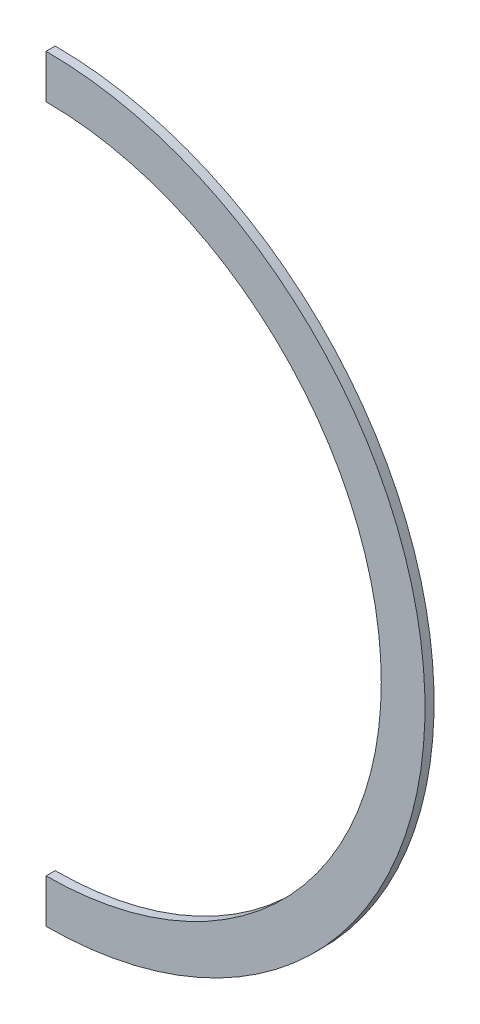
SolidWorks part; units mm, degrees
material "Balsa"
ref_plane "Front Plane" through (0, 0, 0) normal (0, 0, 1) x (1, 0, 0)
ref_plane "Top Plane" through (0, 0, 0) normal (0, 1, 0) x (1, 0, 0)
ref_plane "Right Plane" through (0, 0, 0) normal (1, 0, 0) x (0, 0, -1)
sketch "Sketch2" plane through (0, 0, 0) normal (0, 0, 1) x (1, 0, 0)
  line L0 (0, 0) -> (0, 236.6718) construction
  line L1 (-1.651, 128.5137) -> (-1.651, 121.4017) construction
  line L3 (1.651, 128.5137) -> (1.651, 121.4017) construction
  line L4 (-1.651, 121.4017) -> (1.651, 121.4017) construction
  line L6 (-136.2076, -77.8946) -> (0, 0.7357) construction
  line L8 (136.204, -77.9017) -> (0, 0.7357) construction
  line L9 (-116.9772, -64.8868) -> (-110.0184, -60.8697) construction
  line L10 (-115.4068, -67.793) -> (-108.3676, -63.7294) construction
  line L11 (-110.0184, -60.8697) -> (-108.3676, -63.7294) construction
  line L12 (-117.5534, -65.2194) -> (-116.9772, -64.8868) construction
  line L13 (-115.9025, -68.0791) -> (-115.4068, -67.793) construction
  line L14 (115.4068, -67.793) -> (109.2476, -64.237) construction
  line L15 (110.8986, -61.3773) -> (109.2476, -64.237) construction
  line L16 (116.9772, -64.8868) -> (110.8986, -61.3773) construction
  arc A0 (-1.651, 128.5137) -> (-116.9772, -64.8868) centre (0, -3.556) ccw
  arc A1 (0.0665, 128.1531) -> (63.0696, -118.8475) centre (0, -3.3993) ccw construction
  circle A2 centre (0, -3.556) radius 116.84
  arc A3 (63.0696, -118.8475) -> (0.0665, 128.1531) centre (0, -3.3993) ccw construction
  arc A4 (0, 128.524) -> (-1.651, 128.5137) centre (0, -3.556) ccw
  circle A5 centre (0, -3.556) radius 132.08 construction
  arc A6 (1.651, 128.5137) -> (0, 128.524) centre (0, -3.556) ccw
  arc A7 (-116.9772, -64.8868) -> (-116.2009, -66.3451) centre (0, -3.556) ccw
  arc A8 (-115.4068, -67.793) -> (115.4068, -67.793) centre (0, -3.556) ccw
  arc A9 (-116.2009, -66.3451) -> (-115.4068, -67.793) centre (0, -3.556) ccw
  arc A10 (115.4068, -67.793) -> (116.1977, -66.351) centre (0, -3.556) ccw
  arc A11 (116.9772, -64.8868) -> (1.651, 128.5137) centre (0, -3.556) ccw
  arc A12 (116.1977, -66.351) -> (116.9772, -64.8868) centre (0, -3.556) ccw
  point P24 (-115.4068, -67.793)
  dimension "D1" = 3.556
  dimension "D3" = 264.16
  dimension "D2" = 15.24
  dimension "D4" = 3.302
  dimension "D5" = 7.112
  dimension "D6" = 3.302
  dimension "D7" = 8.128
  dimension "D8" = 7.076
  dimension "D9" = 120.003
  dimension "D10" = 119.997
  dimension "D11" = 0.7357
extrude "Boss-Extrude1" add sketch "Sketch2" along normal mid plane 3.175
sketch "Sketch3" plane through (0, 0, 0) normal (1, 0, 0) x (0, 0, -1)
  line L1 (-109.3908, 192.564) -> (122.8198, 192.564)
  line L2 (-109.3908, 192.564) -> (-109.3908, -206.3906)
  line L3 (-109.3908, -206.3906) -> (122.8198, -206.3906)
  line L4 (122.8198, 192.564) -> (122.8198, -206.3906)
extrude "Cut-Extrude1" cut sketch "Sketch3" against normal through all
